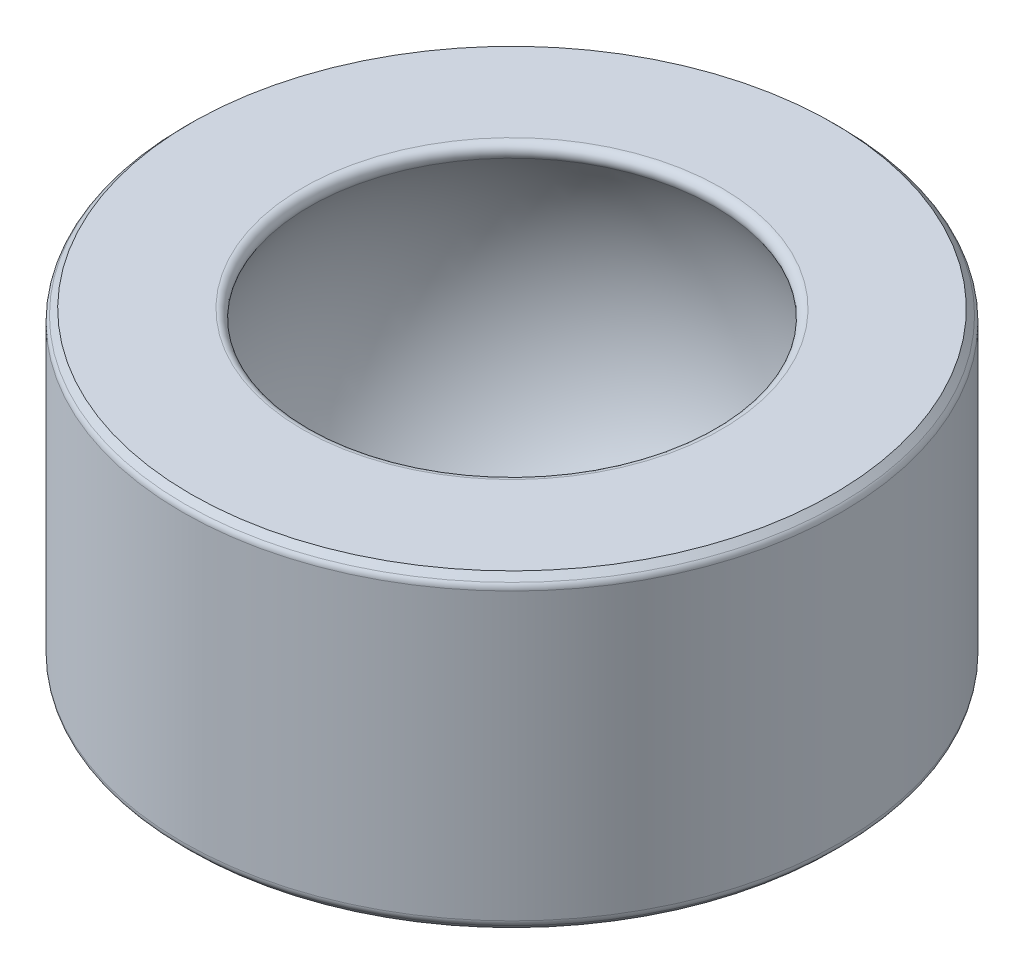
SolidWorks part; units mm, degrees
ref_plane "Front Plane" through (0, 0, 0) normal (0, 0, 1) x (1, 0, 0)
ref_plane "Top Plane" through (0, 0, 0) normal (0, 1, 0) x (1, 0, 0)
ref_plane "Right Plane" through (0, 0, 0) normal (1, 0, 0) x (0, 0, -1)
sketch "Sketch1" plane through (0, 0, 0) normal (0, 1, 0) x (1, 0, 0)
  circle A0 centre (0, 0) radius 2
  circle A1 centre (0, 0) radius 3 construction
  circle A2 centre (0, 0) radius 4
  dimension "D1" = 8
  dimension "D2" = 6
  dimension "D3" = 4
extrude "Boss-Extrude1" add sketch "Sketch1" along normal blind 1.875 and the other way blind 1.875
sketch "Sketch2" plane through (0, 0, 0) normal (0, 1, 0) x (1, 0, 0)
  line L0 (0, 3) -> (0, -3)
  circle A0 centre (0, 0) radius 3 construction
  arc A1 (0, 3) -> (0, -3) centre (0, 0) ccw
revolve "Revolve1" add sketch "Sketch2" angle 360 about L0
combine bodies "Combine1" operation type subtract main body 101 bodies to subtract 102
chamfer "Chamfer1" distance 0.1 angle 45 2 edges at (0, 1.875, 4) (0, -1.875, 4)
fillet "Fillet1" radius 0.1 2 edges at (0, -1.775, 4) (0, 1.775, 4)
fillet "Fillet2" radius 0.1 2 edges at (0, -1.875, 2.3419) (0, 1.875, 2.3419)
